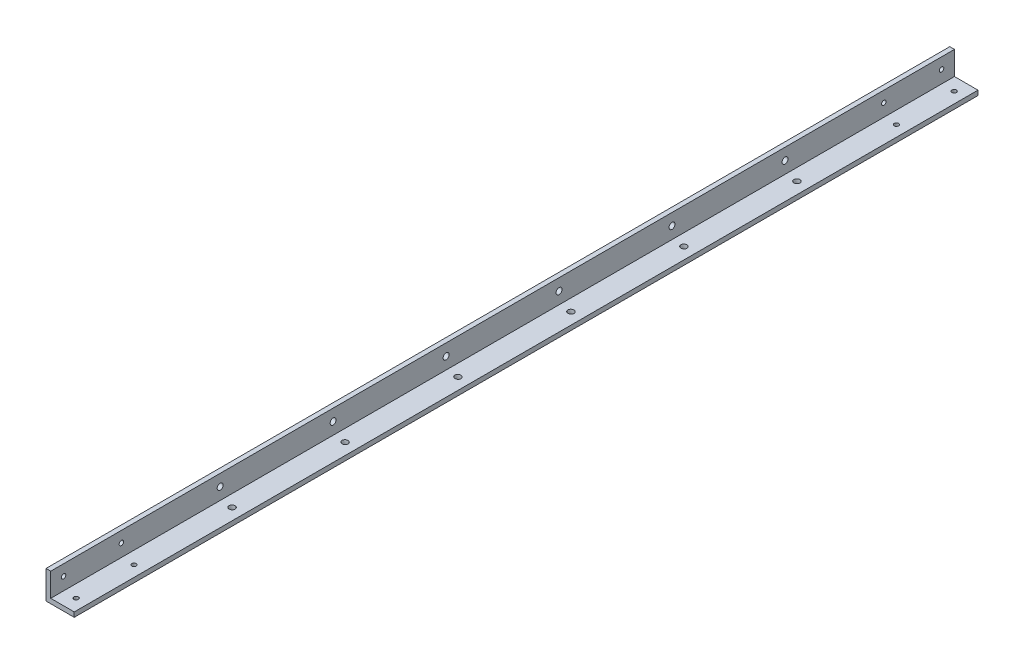
SolidWorks part; units mm, degrees
ref_plane "Front Plane" through (0, 0, 0) normal (0, 0, 1) x (1, 0, 0)
ref_plane "Top Plane" through (0, 0, 0) normal (0, 1, 0) x (1, 0, 0)
ref_plane "Right Plane" through (0, 0, 0) normal (1, 0, 0) x (0, 0, -1)
sketch "Sketch1" plane through (0, 0, 0) normal (0, 0, 1) x (1, 0, 0)
  line L0 (0, 0) -> (19.05, 0)
  line L1 (19.05, 0) -> (19.05, 3.175)
  line L2 (19.05, 3.175) -> (3.175, 3.175)
  line L3 (3.175, 3.175) -> (3.175, 19.05)
  line L4 (3.175, 19.05) -> (0, 19.05)
  line L5 (0, 19.05) -> (0, 0)
  dimension "D1" = 19.05
  dimension "D3" = 3.175
  dimension "D4" = 19.05
extrude "Boss-Extrude1" add sketch "Sketch1" along normal blind 609.6
sketch "Sketch3" plane through (0, 0, 0) normal (0, -1, 0) x (1, 0, 0)
  line L0 (0, 609.6) -> (19.05, 609.6) construction
  line L1 (0, 609.6) -> (0, 0) construction
  line L2 (0, 304.8) -> (50.8099, 304.8) construction
  circle A0 centre (11.671, 600.906) radius 1.5
  circle A1 centre (11.671, 561.94) radius 1.5
  circle A2 centre (11.671, 47.66) radius 1.5
  circle A3 centre (11.671, 8.694) radius 1.5
  dimension "D1" = 8.694
  dimension "D2" = 11.671
  dimension "D3" = 47.66
  dimension "D4" = 3
extrude "Cut-Extrude1" cut sketch "Sketch3" against normal blind 10
sketch "Sketch4" plane through (0, 0, 0) normal (1, 0, 0) x (0, 0, -1)
  line L0 (0, 3.175) -> (0, 19.05) construction
  line L1 (-609.6, 0) -> (0, 0) construction
  line L2 (-609.6, 19.05) -> (0, 19.05) construction
  line L3 (-304.8, 19.05) -> (-304.8, -19.9016) construction
  circle A0 centre (-8.694, 11.671) radius 1.5
  circle A1 centre (-47.66, 11.671) radius 1.5
  circle A2 centre (-600.906, 11.671) radius 1.5
  circle A3 centre (-561.94, 11.671) radius 1.5
  dimension "D1" = 8.694
  dimension "D2" = 11.671
  dimension "D3" = 47.66
extrude "Cut-Extrude4" cut sketch "Sketch4" along normal through all
sketch "Sketch5" plane through (0, 0, 0) normal (1, 0, 0) x (0, 0, -1)
  line L0 (-561.94, 11.671) -> (17.308, 11.671) construction
  line L1 (-609.6, 19.05) -> (0, 19.05) construction
  line L2 (0, 3.175) -> (0, 19.05) construction
  line L5 (-609.6, 3.175) -> (-609.6, 19.05) construction
  circle A0 centre (-342.9, 11.6339) radius 2
  circle A1 centre (-419.1, 11.671) radius 2
  circle A2 centre (-495.3, 11.671) radius 2
  circle A3 centre (-266.7, 11.6339) radius 2
  circle A4 centre (-190.5, 11.671) radius 2
  circle A5 centre (-114.3, 11.671) radius 2
  point P7 (-304.8, 19.05)
  point P22 (-609.6, 11.1125)
  dimension "D1" = 76.2
  dimension "D2" = 76.2
  dimension "D3" = 76.2
  dimension "D4" = 114.3
  dimension "D5" = 76.2
  dimension "D6" = 76.2
  dimension "D7" = 114.3
revolve "Cut-Revolve2" cut sketch "Sketch5" angle 360 about axis through (0, 0, 609.6) along (0, 0, -1)
